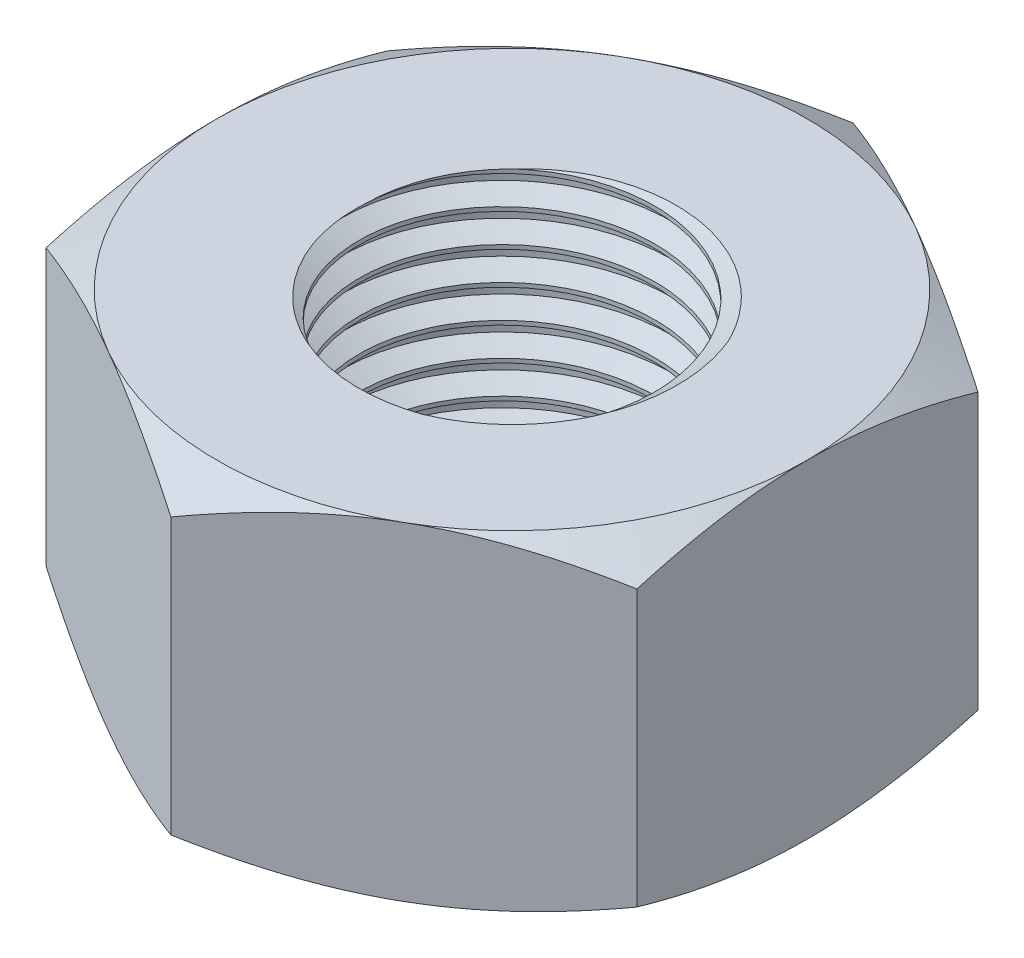
SolidWorks part; units mm, degrees
ref_plane "Front Plane" through (0, 0, 0) normal (0, 0, 1) x (1, 0, 0)
ref_plane "Top Plane" through (0, 0, 0) normal (0, 1, 0) x (1, 0, 0)
ref_plane "Right Plane" through (0, 0, 0) normal (1, 0, 0) x (0, 0, -1)
sketch "Sketch1" plane through (0, 0, 0) normal (0, 1, 0) x (1, 0, 0)
  line L1 (9, -5.1962) -> (9, 5.1962)
  line L2 (9, 5.1962) -> (0, 10.3923)
  line L3 (0, 10.3923) -> (-9, 5.1962)
  line L4 (-9, 5.1962) -> (-9, -5.1962)
  line L5 (-9, -5.1962) -> (0, -10.3923)
  line L6 (0, -10.3923) -> (9, -5.1962)
  circle A0 centre (0, 0) radius 9 construction
  circle A1 centre (0, 0) radius 4.5
  dimension "D2" = 9
  dimension "D1" = 18
extrude "Boss-Extrude1" add sketch "Sketch1" along normal mid plane 10
sketch "Sketch3" plane through (0, 0, 0) normal (0, 0, 1) x (1, 0, 0)
  line L0 (9, -5) -> (10.7056, -5)
  line L1 (10.7056, -5) -> (10.7056, -4.0153)
  line L2 (10.7056, -4.0153) -> (9, -5)
  line L3 (0, 0) -> (50000, 0) construction
  line L4 (0, 0) -> (0, -50000) construction
  line L6 (10.7056, 4.0153) -> (9, 5)
  line L7 (10.7056, 5) -> (10.7056, 4.0153)
  line L8 (9, 5) -> (10.7056, 5)
  dimension "D1" = 30
revolve "Cut-Revolve1" cut sketch "Sketch3" angle 360 about L4
thread "Thread1" pitch 1 method cut profile "Thread Profile1" start angle 0, offset 2, length 14, pitch 1, diameter 9
ref_plane "Plane1" through (-4.5, 7, 0) normal (0, 0, -1) x (1, 0, 0)
sketch "Thread Profile1" plane through (-4.5, 7, 0) normal (0, 0, -1) x (1, 0, 0)
  line L0 (0, 0) -> (0, 1) construction
  line L11 (0, 0) -> (0, 0.875)
  line L12 (0, 0.875) -> (-0.5413, 0.5625)
  line L13 (-0.5413, 0.5625) -> (-0.5413, 0.3125)
  line L15 (-0.5413, 0.3125) -> (0, 0)
  line L17 (-0.5413, 0.4375) -> (0, 0.4375) construction
  point P2 (0, 0)
  dimension "Pitch" = 1
  dimension "Profile_Angle" = 60
  dimension "Profile_Land" = 0.25
  dimension "Profile_Height" = 0.5413
